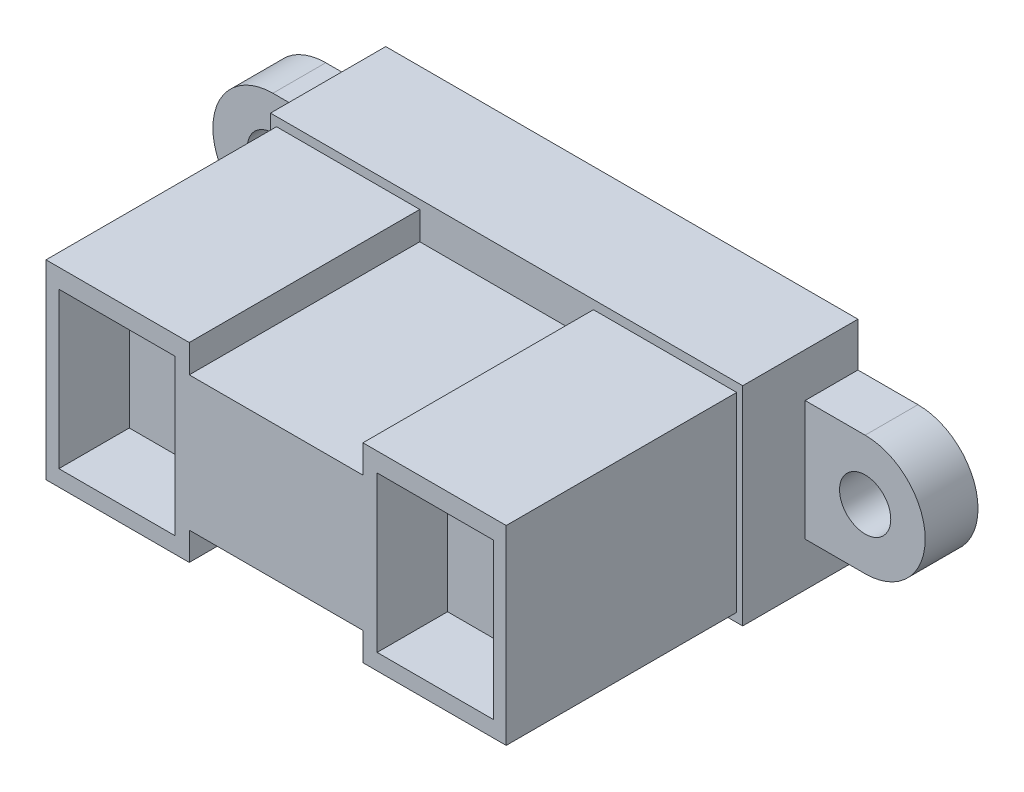
SolidWorks part; units mm, degrees
ref_plane "前视基准面" through (0, 0, 0) normal (0, 0, 1) x (1, 0, 0)
ref_plane "上视基准面" through (0, 0, 0) normal (0, 1, 0) x (1, 0, 0)
ref_plane "右视基准面" through (0, 0, 0) normal (1, 0, 0) x (0, 0, -1)
sketch "草图1" plane through (0, 0, 0) normal (0, 0, 1) x (1, 0, 0)
  line L1 (-18.5, -3.75) -> (18.5, -3.75)
  line L2 (-18.5, -3.75) -> (-18.5, 3.75)
  line L3 (-18.5, 3.75) -> (18.5, 3.75)
  line L4 (18.5, -3.75) -> (18.5, 3.75)
  line L5 (-18.5, -3.75) -> (18.5, 3.75) construction
  line L6 (-18.5, 3.75) -> (18.5, -3.75) construction
  line L7 (-14.75, -6.5) -> (14.75, -6.5)
  line L8 (-14.75, -6.5) -> (-14.75, 6.5)
  line L9 (-14.75, 6.5) -> (14.75, 6.5)
  line L10 (14.75, -6.5) -> (14.75, 6.5)
  line L11 (-14.75, -6.5) -> (14.75, 6.5) construction
  line L12 (-14.75, 6.5) -> (14.75, -6.5) construction
  circle A0 centre (-18.5, 0) radius 3.75
  circle A1 centre (18.5, 0) radius 3.75
  point P0 (0, 0)
  point P10 (0, 0)
  dimension "D3" = 29.5
  dimension "D1" = 37
  dimension "D2" = 7.5
  dimension "D4" = 13
extrude "凸台-拉伸1" add sketch "草图1" along normal blind 3.3 contours A0 L2 | L2 A0 | A0 L8 L3 | A0 L1 L8 | L1 L10 L3 L8 | L4 A1 | A1 L3 L10 | L4 A1 | A1 L10 L1 region at (-15.5876, -2.9124, 0) region at (-20.0915, 0, 0) region at (-16.9085, 0, 0) region at (0, 0, 0) region at (-15.5876, 2.9124, 0) region at (15.5876, -2.9124, 0) region at (16.9085, 0, 0) region at (20.0915, 0, 0) region at (15.5876, 2.9124, 0)
extrude "凸台-拉伸2" add sketch "草图1<3>" along normal blind 21.6 contours L9 L10 L7 L8
sketch "草图1<3>" plane through (0, 0, 0) normal (0, 0, 1) x (1, 0, 0) same geometry as "草图1"
sketch "草图3" plane through (0, 0, 21.6) normal (0, 0, 1) x (1, 0, 0)
  line L0 (0, 0) -> (0, 12.2077) construction
  line L1 (-14.375, 5.95) -> (-5.425, 5.95)
  line L2 (-14.375, 5.95) -> (-14.375, -5.95)
  line L3 (-14.375, -5.95) -> (-5.425, -5.95)
  line L4 (-5.425, 5.95) -> (-5.425, -5.95)
  line L5 (14.375, -5.95) -> (5.425, -5.95)
  line L6 (5.425, 5.95) -> (5.425, -5.95)
  line L7 (14.375, 5.95) -> (5.425, 5.95)
  line L8 (14.375, 5.95) -> (14.375, -5.95)
  line L10 (0, 0) -> (-23.7887, 0) construction
  line L12 (-5.425, 4.2) -> (5.425, 4.2)
  line L13 (-5.425, 4.2) -> (-5.425, -4.2)
  line L14 (-5.425, -4.2) -> (5.425, -4.2)
  line L15 (5.425, 4.2) -> (5.425, -4.2)
  line L16 (-14.75, 6.5) -> (14.75, 6.5)
  line L17 (-14.75, 6.5) -> (-14.75, -6.5)
  line L18 (-14.75, -6.5) -> (14.75, -6.5)
  line L19 (14.75, 6.5) -> (14.75, -6.5)
  point P13 (-9.9, 5.95)
  point P14 (9.9, 5.95)
  line M15 (-14.75, 6.5) -> (-14.75, -6.5)
  line M16 (-14.75, -6.5) -> (14.75, -6.5)
  line M17 (14.75, -6.5) -> (14.75, 6.5)
  line M18 (14.75, 6.5) -> (-14.75, 6.5)
  dimension "D1" = 19.8
  dimension "D2" = 11.9
  dimension "D3" = 8.95
  dimension "D4" = 8.4
extrude "切除-拉伸1" cut sketch "草图3" against normal blind 14.4 contours L14 L4 L3 L2 L1 L12 L6 L7 L8 L5 M18 M15 M16 M17 region at (0, 6.1776, 21.6)
sketch "草图4" plane through (0, 0, 21.6) normal (0, 0, 1) x (1, 0, 0)
  line L0 (0, 0) -> (0, 10.8667) construction
  line L1 (-13.5718, 4.7629) -> (-6.3119, 4.7629)
  line L2 (-13.5718, 4.7629) -> (-13.5718, -4.9478)
  line L3 (-13.5718, -4.9478) -> (-6.3119, -4.9478)
  line L4 (-6.3119, 4.7629) -> (-6.3119, -4.9478)
  line L5 (13.5718, -4.9478) -> (6.3119, -4.9478)
  line L6 (6.3119, 4.7629) -> (6.3119, -4.9478)
  line L7 (13.5718, 4.7629) -> (6.3119, 4.7629)
  line L8 (13.5718, 4.7629) -> (13.5718, -4.9478)
extrude "切除-拉伸2" cut sketch "草图4" against normal blind 4.4
sketch "草图5" plane through (0, -4.2, 0) normal (0, -1, 0) x (1, 0, 0)
  line L0 (-14.75, 0) -> (14.75, 0) construction
  line L1 (-5.05, 4.5) -> (5.05, 4.5)
  line L2 (-5.05, 4.5) -> (-5.05, 3.3)
  line L3 (-5.05, 3.3) -> (5.05, 3.3)
  line L4 (5.05, 4.5) -> (5.05, 3.3)
  line L5 (-2.5288, 5) -> (-2.5288, 7.9417)
  line L6 (-3.0288, 4.5) -> (3.0288, 4.5)
  line L7 (-3.0288, 4.5) -> (-3.0288, 8.4417)
  line L8 (-3.0288, 8.4417) -> (3.0288, 8.4417)
  line L9 (3.0288, 4.5) -> (3.0288, 8.4417)
  line L10 (-2.5288, 7.9417) -> (2.5288, 7.9417)
  line L11 (2.5288, 5) -> (2.5288, 7.9417)
  line L12 (-2.5288, 5) -> (2.5288, 5)
  point P6 (0, 3.3)
  point P12 (0, 8.4417)
  line M9 (-5.425, 7.2) -> (5.425, 7.2)
  dimension "D1" = 3.3
  dimension "D2" = 1.2
  dimension "D3" = 10.1
  dimension "D4" = 0.5
extrude "凸台-拉伸3" add sketch "草图5" along normal offset from surface (8.2 mm away) 18.9 contours L4 L1 L2 L3 region at (0, -4.2, 3.9) up to face at (0, 6.5, 3.6)
extrude "凸台-拉伸4" add sketch "草图5<3>" along normal blind 7.5 contours L5 L12 L11 M9 | L9 L8 L7 L6 region at (0, -4.2, 6.1)
sketch "草图5<3>" plane through (0, -4.2, 0) normal (0, -1, 0) x (1, 0, 0) same geometry as "草图5"
sketch "草图6" plane through (0, 0, 3.3) normal (0, 0, 1) x (1, 0, 0)
  circle A0 centre (-18.5, 0) radius 1.6
  circle A1 centre (18.5, 0) radius 1.6
  dimension "D1" = 3.2
  dimension "D2" = 3.2
extrude "切除-拉伸3" cut sketch "草图6" against normal blind 7.5
sketch "草图7" plane through (0, 0, 0) normal (0, 0, -1) x (-1, 0, 0)
  text T0 "测距传感器\r\n0A02 20-150cm" font "汉仪长仿宋体" height 2.5
